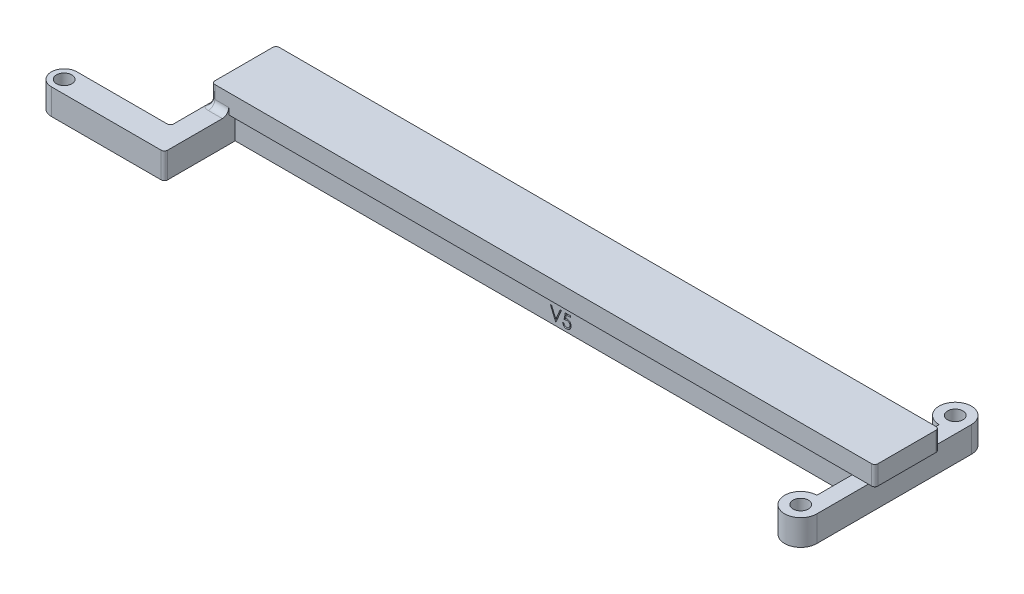
SolidWorks part; units mm, degrees
ref_plane "Front Plane" through (0, 0, 0) normal (0, 0, 1) x (1, 0, 0)
ref_plane "Top Plane" through (0, 0, 0) normal (0, 1, 0) x (1, 0, 0)
ref_plane "Right Plane" through (0, 0, 0) normal (1, 0, 0) x (0, 0, -1)
sketch "Sketch1" plane through (0, 0, 0) normal (0, 1, 0) x (1, 0, 0)
  line L0 (-50.5, 4) -> (-50.5, -4)
  line L1 (-49.5, 3) -> (49.5, 3)
  line L2 (-49.5, 3) -> (-49.5, -3)
  line L3 (-49.5, -3) -> (49.5, -3)
  line L4 (49.5, 3) -> (49.5, -3)
  line L5 (-49.5, 3) -> (49.5, -3) construction
  line L6 (-49.5, -3) -> (49.5, 3) construction
  line L7 (-50.5, -4) -> (50.5, -4)
  line L8 (50.5, 4) -> (50.5, -4)
  line L9 (-50.5, 4) -> (50.5, 4)
  point P0 (0, 0)
  dimension "D1" = 6
  dimension "D2" = 99
  dimension "D3" = 1
extrude "Boss-Extrude1" add sketch "Sketch1" along normal blind 10
sketch "Sketch2" plane through (0, 0, 0) normal (0, -1, 0) x (1, 0, 0)
  line L0 (0, 0) -> (74.3491, 0) construction
  line L1 (48, 0) -> (48, 10.5) construction
  line L2 (50.5, 4) -> (50.5, -4) construction
  line L4 (50.5, 4) -> (67.4224, 4) construction
  line L5 (50.5, -4) -> (69.4178, -4) construction
  line L7 (48, 4) -> (50.5, 4)
  line L9 (48, -4) -> (50.5, -4)
  line L11 (48, 0) -> (48, -8.5) construction
  line L15 (50.5, 4) -> (50.5, 13)
  line L16 (50.5, 13) -> (50, 13) construction
  line L17 (50.5, -4) -> (50.5, -11)
  line L18 (50.5, -11) -> (50, -11) construction
  line L19 (48, 10.5) -> (48, 4)
  line L20 (48, -8.5) -> (48, -4)
  line L21 (-50.5, 4) -> (-50.5, 13) construction
  line L22 (-50.5, 13) -> (-64.4, 13) construction
  line L23 (-66.4, 15) -> (-48.8351, 15)
  line L24 (-48.8351, 15) -> (-48.8351, 4)
  line L25 (-50.5, 4) -> (50.5, 4) construction
  line L26 (-66.4, 11) -> (-51.9017, 11)
  line L27 (-50.5, -4) -> (-59.3527, -4) construction
  line L28 (-51.9017, 11) -> (-51.9017, -4)
  line L29 (-51.9017, -4) -> (-50.5, -4)
  line L30 (-50.5, -4) -> (-50.5, 4)
  line L31 (-50.5, 4) -> (-48.8351, 4)
  line L32 (-64.4, 13) -> (-65.2, 13) construction
  line L33 (-65.2, 13) -> (-66.4, 13) construction
  line L34 (48, 10.5) -> (48, 11) construction
  line L35 (48, 11) -> (48, 13) construction
  line L36 (48, 11) -> (48, 10.5) construction
  line L37 (48, -8.5) -> (48, -9) construction
  line L38 (48, -9) -> (48, -11) construction
  line L39 (48, -9) -> (48, -8.5) construction
  circle A0 centre (48, 13) radius 1.2
  circle A4 centre (48, -11) radius 1.2
  arc A5 (50.5, -11) -> (48, -8.5) centre (48, -11) ccw construction
  arc A8 (48, 10.5) -> (50.5, 13) centre (48, 13) ccw construction
  circle A10 centre (-66.4, 13) radius 1.2
  arc A11 (-66.4, 15) -> (-66.4, 11) centre (-66.4, 13) ccw
  arc A12 (-64.4, 13) -> (-66.4, 15) centre (-66.4, 13) ccw construction
  arc A13 (-66.4, 11) -> (-64.4, 13) centre (-66.4, 13) ccw construction
  arc A14 (50.5, 13) -> (48, 10.5) centre (48, 13) ccw
  arc A15 (48, -8.5) -> (50.5, -11) centre (48, -11) ccw
  dimension "D3" = 2.4
  dimension "D9" = 2.4
  dimension "D10" = 4
  dimension "D1" = 2.5
  dimension "D2" = 13
  dimension "D5" = 11
  dimension "D7" = 9
  dimension "D8" = 15.9
extrude "Boss-Extrude2" add sketch "Sketch2" against normal blind 2
sketch "Sketch3" plane through (0, 10, 0) normal (0, 1, 0) x (1, 0, 0)
  line L0 (51.5, 5) -> (-51.5, 5)
  line L1 (-51.5, 5) -> (-51.5, -5)
  line L2 (-51.5, -5) -> (51.5, -5)
  line L3 (51.5, -5) -> (51.5, 5)
  line L4 (50.5, 4) -> (-50.5, 4)
  line L5 (-50.5, 4) -> (-50.5, -4)
  line L6 (-50.5, -4) -> (50.5, -4)
  line L7 (50.5, -4) -> (50.5, 4)
  line L8 (50.5, 4) -> (-50.5, 4)
  line L9 (-50.5, 4) -> (-50.5, -4)
  line L10 (-50.5, -4) -> (50.5, -4)
  line L11 (50.5, -4) -> (50.5, 4)
  dimension "D1" = 0
  dimension "D2" = 1
extrude "Boss-Extrude3" add sketch "Sketch3" against normal blind 6
fillet "Fillet4" radius 1 1 edges at (0, 4, -4)
fillet "Fillet5" radius 1 1 edges at (0, 4, 4)
fillet "Fillet6" radius 1 1 edges at (50.5, 4, 0)
fillet "Fillet7" radius 1 1 edges at (-50.5, 4, 0)
fillet "Fillet8" radius 0.5 2 edges at (-48.8351, 1, 15) (-51.9017, 1, 11)
fillet "Fillet9" radius 0.5 4 edges at (51.5, 7, -5) (51.5, 7, 5) (-51.5, 7, 5) (-51.5, 7, -5)
sketch "Sketch4" plane through (0, 10, 0) normal (0, 1, 0) x (1, 0, 0)
  line L4 (51.5, -4.5) -> (51.5, 4.5)
  line L5 (51, 5) -> (-51, 5)
  line L6 (-51.5, 4.5) -> (-51.5, -4.5)
  line L7 (-51, -5) -> (51, -5)
  line L8 (51.5, -4.5) -> (51.5, 4.5)
  line L9 (51, 5) -> (-51, 5)
  line L10 (-51.5, 4.5) -> (-51.5, -4.5)
  line L11 (-51, -5) -> (51, -5)
  arc A4 (51.5, 4.5) -> (51, 5) centre (51, 4.5) ccw
  arc A5 (-51, 5) -> (-51.5, 4.5) centre (-51, 4.5) ccw
  arc A6 (-51.5, -4.5) -> (-51, -5) centre (-51, -4.5) ccw
  arc A7 (51, -5) -> (51.5, -4.5) centre (51, -4.5) ccw
  arc A8 (51.5, 4.5) -> (51, 5) centre (51, 4.5) ccw
  arc A9 (-51, 5) -> (-51.5, 4.5) centre (-51, 4.5) ccw
  arc A10 (-51.5, -4.5) -> (-51, -5) centre (-51, -4.5) ccw
  arc A11 (51, -5) -> (51.5, -4.5) centre (51, -4.5) ccw
  dimension "D1" = 0
extrude "Cut-Extrude1" cut sketch "Sketch4" against normal blind 4
sketch "Sketch5" plane through (0, 0, 4) normal (0, 0, 1) x (1, 0, 0)
  text T0 "V5\r\n" font "Century Gothic" height 2
extrude "Cut-Extrude2" cut sketch "Sketch5" against normal blind 0.3
sketch "Sketch7" plane through (0, 6, 0) normal (0, 1, 0) x (1, 0, 0)
  line L4 (51.5, -4.5) -> (51.5, 4.5)
  line L5 (51, 5) -> (-51, 5)
  line L6 (-51.5, 4.5) -> (-51.5, -4.5)
  line L7 (-51, -5) -> (51, -5)
  line L8 (51.5, -4.5) -> (51.5, 4.5)
  line L9 (51, 5) -> (-51, 5)
  line L10 (-51.5, 4.5) -> (-51.5, -4.5)
  line L11 (-51, -5) -> (51, -5)
  arc A4 (51, -5) -> (51.5, -4.5) centre (51, -4.5) ccw
  arc A5 (51.5, 4.5) -> (51, 5) centre (51, 4.5) ccw
  arc A6 (-51, 5) -> (-51.5, 4.5) centre (-51, 4.5) ccw
  arc A7 (-51.5, -4.5) -> (-51, -5) centre (-51, -4.5) ccw
  arc A8 (51, -5) -> (51.5, -4.5) centre (51, -4.5) ccw
  arc A9 (51.5, 4.5) -> (51, 5) centre (51, 4.5) ccw
  arc A10 (-51, 5) -> (-51.5, 4.5) centre (-51, 4.5) ccw
  arc A11 (-51.5, -4.5) -> (-51, -5) centre (-51, -4.5) ccw
  dimension "D1" = 0
extrude "Boss-Extrude4" add sketch "Sketch7" along normal blind 1
sketch "Sketch8" plane through (0, 2, 0) normal (0, 1, 0) x (1, 0, 0)
  line L0 (50.5, 4) -> (50.5, 11) construction
  line L1 (48, 8.5) -> (48, 4) construction
  line L2 (48, 4) -> (50.5, 4) construction
  line L3 (50.5, -13) -> (50.5, -4) construction
  line L4 (50.5, -4) -> (48, -4) construction
  line L5 (48, -4) -> (48, -10.5) construction
  line L6 (-66.4, -15) -> (-49.3351, -15) construction
  line L7 (-48.8351, -14.5) -> (-48.8351, -4) construction
  line L8 (-48.8351, -4) -> (-50.5, -4) construction
  line L9 (-50.5, -4) -> (-50.5, 4) construction
  line L10 (-50.5, 4) -> (-51.9017, 4) construction
  line L11 (-51.9017, 4) -> (-51.9017, -10.5) construction
  line L12 (-52.4017, -11) -> (-66.4, -11) construction
  line L13 (50.5, 4) -> (50.5, 11)
  line L14 (48, 8.5) -> (48, 4)
  line L15 (48, 4) -> (50.5, 4)
  line L16 (50.5, -13) -> (50.5, -4)
  line L17 (50.5, -4) -> (48, -4)
  line L18 (48, -4) -> (48, -10.5)
  line L19 (-66.4, -15) -> (-49.3351, -15)
  line L20 (-48.8351, -14.5) -> (-48.8351, -4)
  line L21 (-48.8351, -4) -> (-50.5, -4)
  line L22 (-50.5, -4) -> (-50.5, 4)
  line L23 (-50.5, 4) -> (-51.9017, 4)
  line L24 (-51.9017, 4) -> (-51.9017, -10.5)
  line L25 (-52.4017, -11) -> (-66.4, -11)
  arc A0 (50.5, 11) -> (48, 8.5) centre (48, 11) ccw construction
  arc A1 (48, -10.5) -> (50.5, -13) centre (48, -13) ccw construction
  arc A2 (-49.3351, -15) -> (-48.8351, -14.5) centre (-49.3351, -14.5) ccw construction
  arc A3 (-52.4017, -11) -> (-51.9017, -10.5) centre (-52.4017, -10.5) ccw construction
  arc A4 (-66.4, -11) -> (-66.4, -15) centre (-66.4, -13) ccw construction
  arc A5 (50.5, 11) -> (48, 8.5) centre (48, 11) ccw
  arc A6 (48, -10.5) -> (50.5, -13) centre (48, -13) ccw
  arc A7 (-49.3351, -15) -> (-48.8351, -14.5) centre (-49.3351, -14.5) ccw
  arc A8 (-52.4017, -11) -> (-51.9017, -10.5) centre (-52.4017, -10.5) ccw
  arc A9 (-66.4, -11) -> (-66.4, -15) centre (-66.4, -13) ccw
  circle A10 centre (48, 11) radius 1.2 construction
  circle A11 centre (48, -13) radius 1.2 construction
  circle A12 centre (-66.4, -13) radius 1.2 construction
  circle A13 centre (48, 11) radius 1.2
  circle A14 centre (48, -13) radius 1.2
  circle A15 centre (-66.4, -13) radius 1.2
extrude "Boss-Extrude5" add sketch "Sketch8" along normal blind 2
fillet "Fillet10" radius 1 3 edges at (-49.9175, 4, 5) (-51.3536, 4, 4.8536) (-51.5, 4, 0.25)
